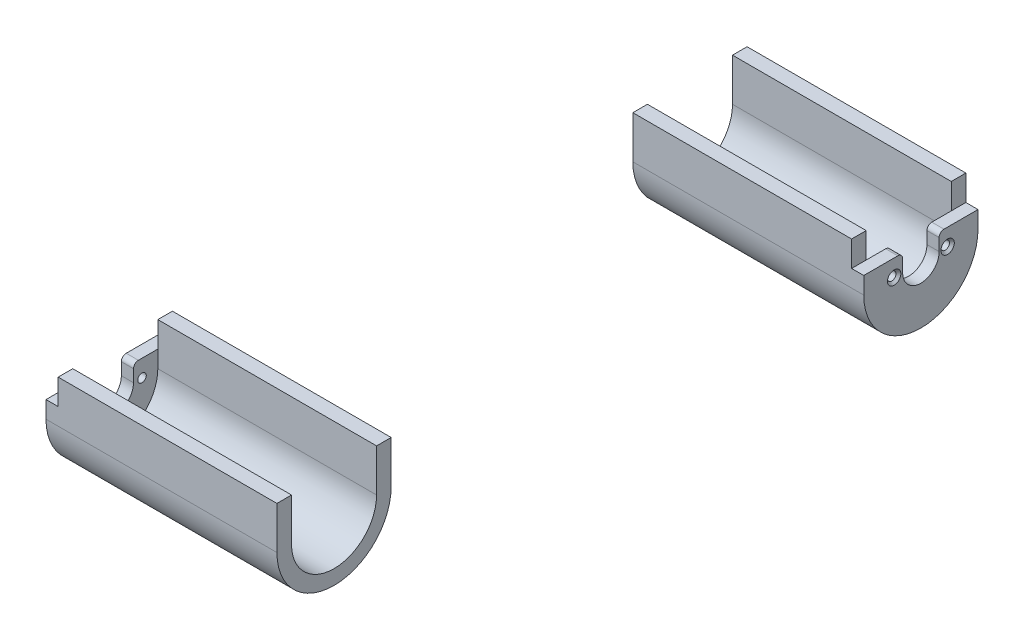
SolidWorks part; units mm, degrees
ref_plane "Front Plane" through (0, 0, 0) normal (0, 0, 1) x (1, 0, 0)
ref_plane "Top Plane" through (0, 0, 0) normal (0, 1, 0) x (1, 0, 0)
ref_plane "Right Plane" through (0, 0, 0) normal (1, 0, 0) x (0, 0, -1)
ref_axis "Center Axis" through (0, 23.7128, 0) along (0, -1, 0)
sketch "Sketch1" plane through (0, 0, 0) normal (1, 0, 0) x (0, 0, -1)
  line L0 (-159.8432, -20) -> (183.538, -20) construction
  line L1 (23.9696, -38.5304) -> (68.7681, 6.2681) construction
  line L2 (44.3566, -9.3934) -> (44.3566, -0.6434)
  line L3 (61.8566, -9.3934) -> (61.8566, -0.6434)
  line L4 (64.8566, -9.3934) -> (64.8566, -0.6434)
  line L5 (41.3566, -9.3934) -> (41.3566, -0.6434)
  line L6 (41.3566, -0.6434) -> (44.3566, -0.6434)
  line L7 (61.8566, -0.6434) -> (64.8566, -0.6434)
  arc A0 (44.3566, -9.3934) -> (61.8566, -9.3934) centre (53.1066, -9.3934) ccw
  arc A1 (41.3566, -9.3934) -> (64.8566, -9.3934) centre (53.1066, -9.3934) ccw
  point P1 (42.5, -20)
  dimension "D1" = 20
  dimension "D4" = 8.75
  dimension "D2" = 42.5
  dimension "D3" = 45
  dimension "D5" = 8.75
  dimension "D6" = 15
  dimension "D7" = 3
extrude "FrontMotorBracket" add sketch "Sketch1" along normal blind 45 from offset 16.5 offset against normal yes
sketch "Sketch8" plane through (0, 0, 0) normal (1, 0, 0) x (0, 0, -1)
  line L0 (-79.9426, -20) -> (109.5131, -20) construction
  line L1 (-68.835, 6.335) -> (-18.9148, -43.5852) construction
  line L2 (-61.8566, -9.3934) -> (-61.8566, -0.6434)
  line L3 (-41.3566, -0.6434) -> (-41.3566, -9.3934)
  line L4 (-44.3566, -0.6434) -> (-44.3566, -9.3934)
  line L5 (-64.8566, -9.3934) -> (-64.8566, -0.6434)
  line L6 (-64.8566, -0.6434) -> (-61.8566, -0.6434)
  line L7 (-44.3566, -0.6434) -> (-41.3566, -0.6434)
  arc A0 (-61.8566, -9.3934) -> (-44.3566, -9.3934) centre (-53.1066, -9.3934) ccw
  arc A1 (-64.8566, -9.3934) -> (-41.3566, -9.3934) centre (-53.1066, -9.3934) ccw
  point P5 (-42.5, -20)
  dimension "D5" = 8.75
  dimension "D1" = 20
  dimension "D2" = 42.5
  dimension "D3" = 45
  dimension "D4" = 15
  dimension "D6" = 8.75
  dimension "D7" = 3
extrude "RearMotorBracket" add sketch "Sketch8" against normal blind 45 from offset 16.5 separate body
sketch "Sketch5" plane through (28.5, 0, 0) normal (1, 0, 0) x (0, 0, -1)
  line L0 (49.3566, -6.8934) -> (49.3566, -9.3934)
  line L1 (41.3566, -9.3934) -> (41.3566, -5.8934)
  line L3 (41.3566, -5.8934) -> (48.3566, -5.8934)
  line L4 (41.3566, -0.6434) -> (41.3566, -9.3934) construction
  line L5 (56.8566, -6.8934) -> (56.8566, -9.3934)
  line L6 (57.8566, -5.8934) -> (64.8566, -5.8934)
  line L7 (64.8566, -9.3934) -> (64.8566, -0.6434) construction
  line L8 (64.8566, -5.8934) -> (64.8566, -9.3934)
  arc A0 (41.3566, -9.3934) -> (64.8566, -9.3934) centre (53.1066, -9.3934) ccw construction
  arc A1 (41.3566, -9.3934) -> (64.8566, -9.3934) centre (53.1066, -9.3934) ccw
  arc A3 (48.3566, -5.8934) -> (49.3566, -6.8934) centre (48.3566, -6.8934) cw
  arc A4 (49.3566, -9.3934) -> (56.8566, -9.3934) centre (53.1066, -9.3934) ccw
  arc A5 (49.3566, -9.3934) -> (56.8566, -9.3934) centre (53.1066, -9.3934) ccw
  arc A6 (57.8566, -5.8934) -> (56.8566, -6.8934) centre (57.8566, -6.8934) ccw
  dimension "D3" = 1
  dimension "D4" = 1
  dimension "D2" = 3.5
  dimension "D1" = 5
extrude "FrontMotorPlate" add sketch "Sketch5" along normal blind 2.5
sketch "Sketch9" plane through (-28.5, 0, 0) normal (-1, 0, 0) x (0, 0, 1)
  line L0 (41.3566, -9.3934) -> (41.3566, -5.8934)
  line L1 (41.3566, -9.3934) -> (41.3566, -0.6434) construction
  line L2 (41.3566, -5.8934) -> (48.3566, -5.8934)
  line L3 (49.3566, -6.8934) -> (49.3566, -9.3934)
  line L4 (56.8566, -9.3934) -> (56.8566, -6.8934)
  line L5 (57.8566, -5.8934) -> (64.8566, -5.8934)
  line L6 (64.8566, -0.6434) -> (64.8566, -9.3934) construction
  line L7 (64.8566, -5.8934) -> (64.8566, -9.3934)
  arc A0 (41.3566, -9.3934) -> (64.8566, -9.3934) centre (53.1066, -9.3934) ccw construction
  arc A1 (41.3566, -9.3934) -> (64.8566, -9.3934) centre (53.1066, -9.3934) ccw
  arc A4 (48.3566, -5.8934) -> (49.3566, -6.8934) centre (48.3566, -6.8934) cw
  arc A5 (49.3566, -9.3934) -> (56.8566, -9.3934) centre (53.1066, -9.3934) ccw
  arc A6 (49.3566, -9.3934) -> (56.8566, -9.3934) centre (53.1066, -9.3934) ccw
  arc A7 (56.8566, -6.8934) -> (57.8566, -5.8934) centre (57.8566, -6.8934) cw
  dimension "D3" = 1
  dimension "D4" = 1
  dimension "D2" = 3.5
  dimension "D1" = 5
extrude "RearMotorPlate" add sketch "Sketch9" along normal blind 2.5
sketch "Sketch6" plane through (31, 0, 0) normal (1, 0, 0) x (0, 0, -1)
  line L0 (35.2696, -9.3934) -> (72.8501, -9.3934) construction
  line L1 (53.1066, 12.6171) -> (53.1066, -36.011) construction
  arc A0 (49.3566, -9.3934) -> (56.8566, -9.3934) centre (53.1066, -9.3934) ccw construction
  arc A1 (49.3566, -9.3934) -> (56.8566, -9.3934) centre (53.1066, -9.3934) ccw construction
  circle A2 centre (47.6066, -9.3934) radius 0.875
  circle A3 centre (58.6066, -9.3934) radius 0.875
  dimension "D2" = 1.75
  dimension "D1" = 11
extrude "FrontMotorScrewHoles" cut sketch "Sketch6" against normal up to next (2.5 mm away)
sketch "Sketch10" plane through (-31, 0, 0) normal (-1, 0, 0) x (0, 0, 1)
  line L0 (33.7961, -9.3934) -> (79.1637, -9.3934) construction
  line L1 (53.1066, 11.6109) -> (53.1066, -30.6773) construction
  arc A0 (49.3566, -9.3934) -> (56.8566, -9.3934) centre (53.1066, -9.3934) ccw construction
  arc A1 (49.3566, -9.3934) -> (56.8566, -9.3934) centre (53.1066, -9.3934) ccw construction
  circle A2 centre (47.6066, -9.3934) radius 0.875
  circle A3 centre (58.6066, -9.3934) radius 0.875
  dimension "D1" = 1.75
  dimension "D2" = 11
extrude "RearMotorScrewHoles" cut sketch "Sketch10" against normal up to next (2.5 mm away)
chamfer "FrontMotorScrewChamfer" distance 0.5 angle 45 2 edges at (31, -9.3934, -59.4816) (31, -9.3934, -48.4816)
chamfer "RearMotorScrewChamfer" distance 0.5 angle 45 2 edges at (-31, -9.3934, 59.4816) (-31, -9.3934, 48.4816)
